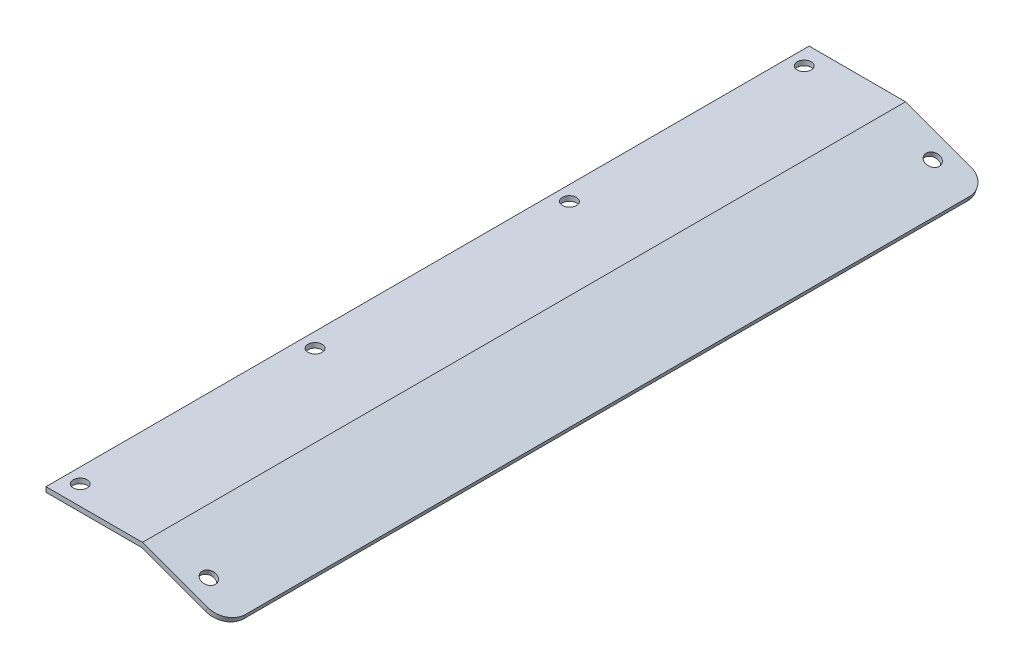
SolidWorks part; units mm, degrees
ref_plane "Front Plane" through (0, 0, 0) normal (0, 0, 1) x (1, 0, 0)
ref_plane "Top Plane" through (0, 0, 0) normal (0, 1, 0) x (1, 0, 0)
ref_plane "Right Plane" through (0, 0, 0) normal (1, 0, 0) x (0, 0, -1)
sketch "Sketch1" plane through (0, 0, 0) normal (0, 0, 1) x (1, 0, 0)
  line L0 (0, 0) -> (31.0189, 0)
  line L1 (31.0189, 0) -> (57.8706, -9.7732)
  line L2 (57.8706, -9.7732) -> (58.4135, -8.2815)
  line L3 (58.4135, -8.2815) -> (31.2988, 1.5875)
  line L4 (31.2988, 1.5875) -> (0, 1.5875)
  line L5 (0, 1.5875) -> (0, 0)
  line L9 (31.2819, -0.0957) -> (54.9047, -8.6937) construction
  point P5 (19.6896, 1.5875)
  point P8 (25.227, 0)
  point P14 (31.0189, 0)
  dimension "D1" = 1.5875
  dimension "D2" = 1.5875
  dimension "D3" = 28.575
extrude "Boss-Extrude1" add sketch "Sketch1" along normal up to surface (247.65 mm away)
sketch "Sketch2" plane through (0, 1.5875, 0) normal (0, 1, 0) x (1, 0, 0)
  line L0 (0, -247.65) -> (0, 0) construction
  line L1 (31.2988, 0) -> (0, 0) construction
  line L2 (31.2988, -247.65) -> (0, -247.65) construction
  circle A0 centre (4.7625, -6.35) radius 2.286
  circle A1 centre (4.7625, -241.3) radius 2.286
  circle A2 centre (4.7625, -82.55) radius 2.286
  circle A3 centre (4.7625, -165.1) radius 2.286
  point P14 (0, 0)
  dimension "D3" = 4.572
  dimension "D1" = 4.7625
  dimension "D2" = 6.35
  dimension "D4" = 6.35
  dimension "D5" = 76.2
  dimension "D6" = 76.2
extrude "Cut-Extrude1" cut sketch "Sketch2" against normal through all
sketch "Sketch3" plane through (4.1715, 11.461, 0) normal (0.342, 0.9397, 0) x (0.9397, -0.342, 0)
  line L0 (57.7232, 0) -> (28.8683, 0) construction
  line L5 (57.7232, -247.65) -> (57.7232, 0) construction
  line L6 (57.7232, -247.65) -> (28.8683, -247.65) construction
  circle A0 centre (45.0232, -6.35) radius 2.286
  circle A1 centre (45.0232, -241.3) radius 2.286
  point P10 (0, 0)
  point P11 (0, 0)
  dimension "D3" = 4.572
  dimension "D1" = 6.35
  dimension "D2" = 12.7
  dimension "D4" = 6.35
extrude "Cut-Extrude2" cut sketch "Sketch3" against normal through all
fillet "Fillet1" radius 6.35 2 edges at (58.1421, -9.0273, 0) (58.1421, -9.0273, 247.65)
